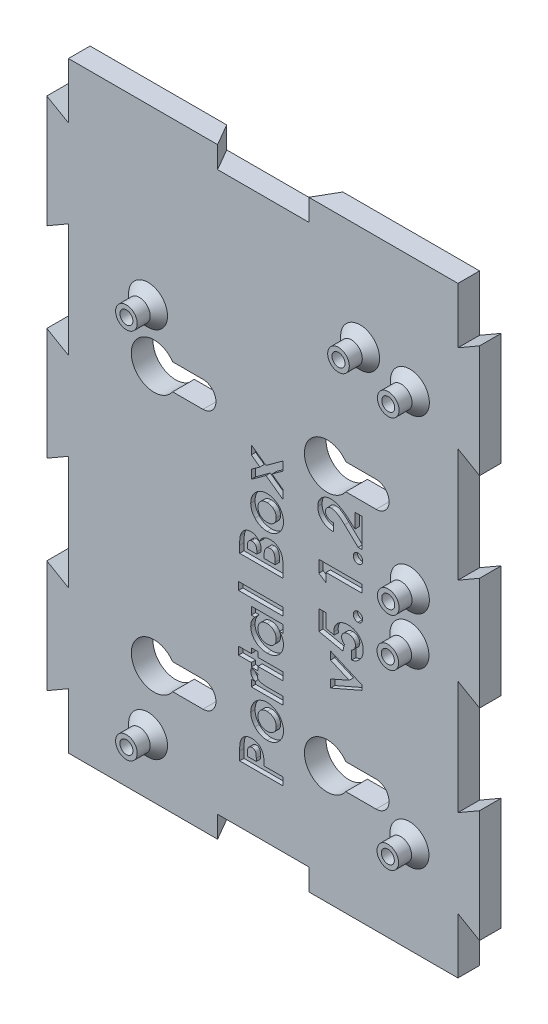
SolidWorks part; units mm, degrees
ref_plane "Front Plane" through (0, 0, 0) normal (1, 0, 0) x (0, 1, 0)
ref_plane "Top Plane" through (0, 0, 0) normal (0, 0, 1) x (0, 1, 0)
ref_plane "Right Plane" through (0, 0, 0) normal (0, 1, 0) x (-1, 0, 0)
sketch "Sketch2" plane through (0, 0, 0) normal (0, 0, 1) x (0, 1, 0)
  line L1 (-60.1282, -37.9423) -> (59.8718, -37.9423) construction
  line L2 (-60.1282, -37.9423) -> (-60.1282, 42.0577) construction
  line L3 (-60.1282, 42.0577) -> (59.8718, 42.0577) construction
  line L4 (59.8718, -37.9423) -> (59.8718, 42.0577) construction
  line L13 (-72.6282, 49.5577) -> (66.3718, 49.5577)
  line L14 (-72.6282, 49.5577) -> (-72.6282, -40.4423)
  line L15 (-72.6282, -40.4423) -> (66.3718, -40.4423)
  line L16 (66.3718, 49.5577) -> (66.3718, -40.4423)
  point P0 (0, 0)
  point P6 (0, 0)
  dimension "D1" = 120
  dimension "D2" = 80
  dimension "D3" = 12.5
  dimension "D5" = 139
  dimension "D6" = 90
  dimension "D7" = 7.5
extrude "Boss-Extrude1" add sketch "Sketch2" along normal blind 5
sketch "Sketch9" plane through (0, 0, 5) normal (0, 0, 1) x (1, 0, 0)
  line L0 (0, 9.5784) -> (0, -57.7301) construction
  text T0 "<b>Portal Box</b>\r\n<b> v5.1.2</b>" font "Century Gothic" height 10
  point P3 (0, -57.7301)
  point P4 (0, 9.5784)
extrude "Cut-Extrude4" cut sketch "Sketch9" against normal blind 1
sketch "Sketch12" plane through (0, 0, 5) normal (0, 0, 1) x (1, 0, 0)
  line L0 (-54.5577, 30.3911) -> (-54.5577, 56.3718)
  line L1 (-54.5577, 56.3718) -> (-32.0577, 43.3815)
  line L2 (-32.0577, 43.3815) -> (-54.5577, 30.3911)
  line L4 (-32.0577, -3.1282) -> (-54.5577, -16.1185)
  line L5 (-54.5577, -16.1185) -> (-54.5577, 9.8622)
  line L6 (-54.5577, 9.8622) -> (-32.0577, -3.1282)
  line L7 (-32.0577, -49.6378) -> (-54.5577, -62.6282)
  line L8 (-54.5577, -62.6282) -> (-54.5577, -36.6474)
  line L9 (-54.5577, -36.6474) -> (-32.0577, -49.6378)
  line L11 (0, 70.08) -> (0, -71.8273) construction
  line L12 (0, -2.75) -> (0, 2.75) construction
  line L22 (-49.5577, 66.3718) -> (-49.5577, -72.6282) construction
  line L23 (40.4423, 66.3718) -> (-49.5577, 66.3718) construction
  line L24 (-49.5577, -72.6282) -> (40.4423, -72.6282) construction
  line L26 (-4.5577, 66.3718) -> (-4.5577, -72.6282) construction
  line L28 (45.4423, 56.3718) -> (22.9423, 43.3815)
  line L29 (45.4423, 30.3911) -> (45.4423, 56.3718)
  line L30 (22.9423, 43.3815) -> (45.4423, 30.3911)
  line L31 (45.4423, 9.8622) -> (22.9423, -3.1282)
  line L32 (45.4423, -16.1185) -> (45.4423, 9.8622)
  line L33 (22.9423, -3.1282) -> (45.4423, -16.1185)
  line L34 (45.4423, -36.6474) -> (22.9423, -49.6378)
  line L35 (45.4423, -62.6282) -> (45.4423, -36.6474)
  line L36 (22.9423, -49.6378) -> (45.4423, -62.6282)
  circle A0 centre (-47.0577, 43.3815) radius 7.5
  dimension "D1" = 15
  dimension "D2" = 5
  dimension "D4" = 10
  dimension "D5" = 10
  dimension "D9" = 20.5289
  dimension "D10" = 20.5289
  dimension "D3" = 3
extrude "Boss-Extrude5" add sketch "Sketch12" against normal blind 5 contours L9 L8 L7 | L6 L5 L4 | A0 L0 L2 | A0 | A0 L1 L0 | A0 L2 L1 | L34 | L31 | L28 L30 L29 region at (-51.7998, 35.168, 5) region at (-51.7998, 51.5949, 5) region at (-47.0577, 43.3815, 5) region at (-37.5737, 43.3815, 5) region at (-47.0577, -3.1282, 5) region at (-47.0577, -49.6378, 5) region at (37.9423, -3.1282, 5) region at (37.9423, -49.6378, 5)
sketch "Sketch13" plane through (0, 66.3718, -60) normal (0, 1, 0) x (1, 0, 0)
  line L0 (-17.9811, -60) -> (8.8657, -60)
  line L1 (8.8657, -60) -> (-4.5577, -83.25)
  line L2 (-4.5577, -83.25) -> (-17.9811, -60)
  line L5 (40.4423, -65) -> (40.4423, -60) construction
  line L6 (-49.5, -60) -> (49.5, -60) construction
  circle A0 centre (-4.5577, -67.75) radius 7.75
  dimension "D1" = 15.5
  dimension "D2" = 0
  dimension "D3" = 45
extrude "Cut-Extrude5" cut sketch "Sketch13" along normal blind 5 from surface contours L1 L2 L0 starting at face at (-4.5577, -72.6282, 2.5)
extrude "Cut-Extrude6" cut sketch "Sketch13<3>" against normal blind 5 contours L0 L1 L2
sketch "Sketch13<3>" plane through (0, 66.3718, -60) normal (0, 1, 0) x (1, 0, 0) same geometry as "Sketch13"
sketch "Sketch11" plane through (0, 0, 5) normal (0, 0, 1) x (1, 0, 0)
  line L0 (-44.5577, 56.3718) -> (35.4423, 56.3718) construction
  line L1 (-44.5577, 56.3718) -> (-44.5577, -63.6282) construction
  line L2 (-44.5577, -63.6282) -> (35.4423, -63.6282) construction
  line L3 (35.4423, 56.3718) -> (35.4423, -63.6282) construction
  line L4 (-44.5577, 56.3718) -> (35.4423, -63.6282) construction
  line L5 (-44.5577, -63.6282) -> (35.4423, 56.3718) construction
  line L7 (-49.5577, -72.6282) -> (-15.0944, -72.6282) construction
  line L8 (-49.5577, -13.2318) -> (-49.5577, -39.5342) construction
  line L9 (40.4423, 53.4851) -> (40.4423, 66.3718) construction
  circle A0 centre (-31.1577, -59.7282) radius 2.5
  circle A1 centre (-31.1577, 26.2718) radius 2.5
  circle A2 centre (17.8423, 42.2718) radius 1.5
  circle A3 centre (17.8423, 42.2718) radius 2.5
  circle A4 centre (-31.1577, 26.2718) radius 1.5
  circle A5 centre (-31.1577, -59.7282) radius 1.5
  circle A6 centre (29.2423, -51.4282) radius 1.5
  circle A7 centre (29.2423, -11.4282) radius 1.5
  circle A8 centre (29.2423, -51.4282) radius 2.5
  circle A9 centre (29.2423, -11.4282) radius 2.5
  circle A10 centre (29.3423, 39.1718) radius 1.5
  circle A11 centre (29.3423, -0.3282) radius 1.5
  circle A12 centre (29.3423, 39.1718) radius 2.5
  circle A13 centre (29.3423, -0.3282) radius 2.5
  point P6 (0, 0)
  dimension "D5" = 3
  dimension "D6" = 5
  dimension "D8" = 5
  dimension "D9" = 3
  dimension "D11" = 5
  dimension "D12" = 3
  dimension "D17" = 3
  dimension "D18" = 3
  dimension "D19" = 5
  dimension "D20" = 5
  dimension "D25" = 3
  dimension "D26" = 3
  dimension "D27" = 5
  dimension "D28" = 5
  dimension "D1" = 80
  dimension "D2" = 120
  dimension "D3" = 14.1
  dimension "D4" = 17.6
  dimension "D7" = 13.4
  dimension "D10" = 3.9
  dimension "D13" = 12.2
  dimension "D14" = 6.2
  dimension "D15" = 52.2
  dimension "D16" = 6.2
  dimension "D21" = 6.1
  dimension "D22" = 6.1
  dimension "D23" = 56.7
  dimension "D24" = 17.2
  dimension "D29" = 13.4
  dimension "D30" = 30.1
  dimension "D31" = 9
  dimension "D32" = 5
  dimension "D33" = 5
extrude "Boss-Extrude4" add sketch "Sketch11" along normal blind 5
chamfer "Chamfer1" distance 2 angle 45 7 edges at (-28.6577, 26.2718, 5) (-28.6577, -59.7282, 5) (31.7423, -51.4282, 5) (31.7423, -11.4282, 5) (31.8423, -0.3282, 5) (31.8423, 39.1718, 5) (20.3423, 42.2718, 5)
sketch "Sketch14" plane through (0, 0, 0) normal (0, 0, -1) x (1, 0, 0)
  line L0 (21.529, 48.2891) -> (14.529, 48.2891)
  line L1 (21.529, 42.2891) -> (14.529, 42.2891)
  line L2 (21.529, -11.7109) -> (14.529, -11.7109)
  line L3 (21.529, -17.7109) -> (14.529, -17.7109)
  line L4 (-18.471, 48.2891) -> (-25.471, 48.2891)
  line L5 (-18.471, 42.2891) -> (-25.471, 42.2891)
  line L6 (-18.471, -11.7109) -> (-25.471, -11.7109)
  line L7 (-18.471, -17.7109) -> (-25.471, -17.7109)
  line L8 (14.529, 42.2891) -> (14.529, 48.2891)
  line L9 (21.529, 48.2891) -> (21.529, 42.2891)
  line L10 (-25.471, 48.2891) -> (-25.471, 42.2891)
  line L11 (-18.471, 48.2891) -> (-18.471, 42.2891)
  line L12 (-25.471, -11.7109) -> (-25.471, -17.7109)
  line L13 (-18.471, -11.7109) -> (-18.471, -17.7109)
  line L14 (14.529, -11.7109) -> (14.529, -17.7109)
  line L15 (21.529, -11.7109) -> (21.529, -17.7109)
  circle A2 centre (21.529, 45.2891) radius 3
  circle A3 centre (21.529, -14.7109) radius 3
  circle A4 centre (10.2206, 45.2891) radius 5.25
  circle A5 centre (10.2206, -14.7109) radius 5.25
  circle A6 centre (-18.471, 45.2891) radius 3
  circle A7 centre (-18.471, -14.7109) radius 3
  circle A8 centre (-29.7794, 45.2891) radius 5.25
  circle A9 centre (-29.7794, -14.7109) radius 5.25
  point P32 (-30.0001, 37.2152)
  point P33 (-29.7794, 45.2891)
  dimension "D1" = 6
  dimension "D2" = 10.5
  dimension "D3" = 10.5
  dimension "D4" = 6
  dimension "D5" = 10.5
  dimension "D6" = 10.5
  dimension "D7" = 7
  dimension "D8" = 7
  dimension "D9" = 7
  dimension "D10" = 7
  dimension "D11" = 7
  dimension "D12" = 7
  dimension "D13" = 7
  dimension "D14" = 7
  dimension "D15" = 40
  dimension "D16" = 60
extrude "Cut-Extrude7" cut sketch "Sketch14" against normal blind 10 contours A5 | L3 L14 L2 L15 | A3 | A9 | L7 L12 L6 L13 | A7 | A8 | L5 L10 L4 L11 | A6 | A4 | L1 L8 L0 L9 | A2
